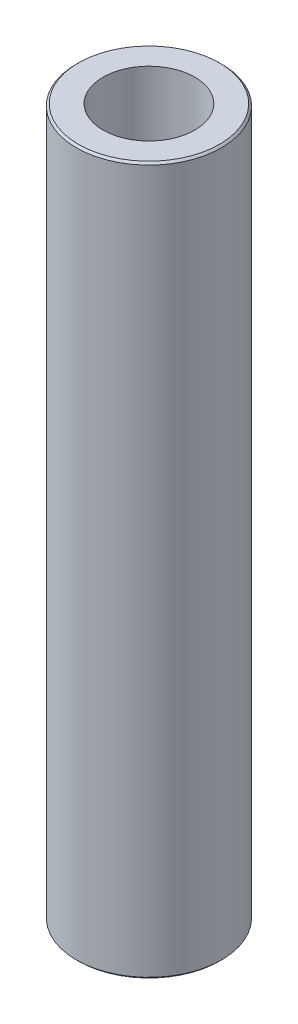
SolidWorks part; units mm, degrees
ref_plane "Front Plane" through (0, 0, 0) normal (0, 0, 1) x (1, 0, 0)
ref_plane "Top Plane" through (0, 0, 0) normal (0, 1, 0) x (1, 0, 0)
ref_plane "Right Plane" through (0, 0, 0) normal (1, 0, 0) x (0, 0, -1)
sketch "Sketch1" plane through (0, 0, 0) normal (0, 1, 0) x (1, 0, 0)
  circle A0 centre (0, 0) radius 25
  dimension "SHAFT_OD" = 50
extrude "Boss-Extrude1" add sketch "Sketch1" along normal blind 243.6372
sketch "Sketch2" plane through (0, 0, 0) normal (0, 1, 0) x (1, 0, 0)
  circle A0 centre (0, 0) radius 15.8059
  dimension "BORE_D" = 31.6118
extrude "Cut-Extrude1" cut sketch "Sketch2" along normal through all
chamfer "Chamfer1" distance 0.678 angle 45.64 2 edges at (0, 243.6372, 25) (0, 0, 25) first distance on face at (0, 243.6372, 25) first distance on face at (0, 0, 15.8059)
